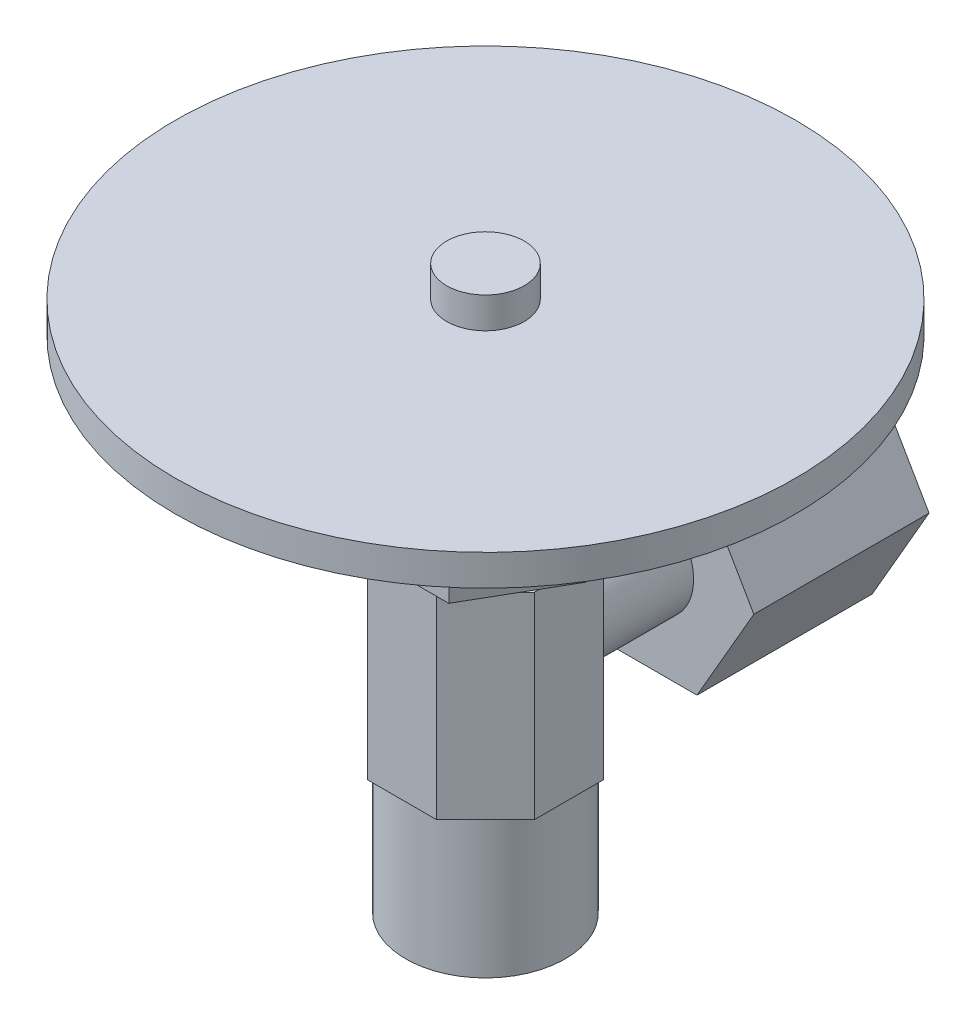
SolidWorks part; units mm, degrees
ref_plane "Front Plane" through (0, 0, 0) normal (0, 0, 1) x (1, 0, 0)
ref_plane "Top Plane" through (0, 0, 0) normal (0, 1, 0) x (1, 0, 0)
ref_plane "Right Plane" through (0, 0, 0) normal (1, 0, 0) x (0, 0, -1)
sketch "Sketch1" plane through (0, 0, 0) normal (0, 1, 0) x (1, 0, 0)
  line L0 (-2.2264, -5.375) -> (2.2264, -5.375)
  line L1 (5.375, -2.2264) -> (5.375, 2.2264)
  line L2 (5.375, 2.2264) -> (2.2264, 5.375)
  line L3 (2.2264, 5.375) -> (-2.2264, 5.375)
  line L4 (-2.2264, 5.375) -> (-5.375, 2.2264)
  line L5 (-5.375, 2.2264) -> (-5.375, -2.2264)
  line L6 (-5.375, -2.2264) -> (-2.2264, -5.375)
  line L7 (2.2264, -5.375) -> (5.375, -2.2264)
  circle A0 centre (0, 0) radius 5.375 construction
  dimension "D1" = 10.75
extrude "Boss-Extrude1" add sketch "Sketch1" along normal blind 12.7
sketch "Sketch2" plane through (0, 0, -5.375) normal (0, 0, -1) x (-1, 0, 0)
  line L0 (-2.2264, 12.7) -> (2.2264, 0) construction
  line L1 (2.2264, 0) -> (5.375, 0) construction
  line L2 (2.2264, 12.7) -> (2.2264, 0) construction
  circle A0 centre (0, 6.35) radius 3.445
extrude "Boss-Extrude2" add sketch "Sketch2" along normal blind 4.6 and the other way blind 2
sketch "Sketch3" plane through (0, 0, -9.975) normal (0, 0, -1) x (-1, 0, 0)
  line L1 (7.3323, 6.35) -> (3.6662, 12.7)
  line L2 (3.6662, 12.7) -> (-3.6662, 12.7)
  line L3 (-3.6662, 12.7) -> (-7.3323, 6.35)
  line L4 (-7.3323, 6.35) -> (-3.6662, 0)
  line L5 (-3.6662, 0) -> (3.6662, 0)
  line L6 (3.6662, 0) -> (7.3323, 6.35)
  circle A0 centre (0, 6.35) radius 6.35 construction
  dimension "D1" = 12.7
extrude "Boss-Extrude3" add sketch "Sketch3" along normal blind 11.3
sketch "Sketch4" plane through (0, 0, 0) normal (0, -1, 0) x (1, 0, 0)
  circle A0 centre (0, 0) radius 5.15
  dimension "D1" = 10.3
extrude "Boss-Extrude4" add sketch "Sketch4" along normal blind 9
sketch "Sketch5" plane through (0, 12.7, 0) normal (0, 1, 0) x (1, 0, 0)
  line L1 (6.4663, 0) -> (3.2332, 5.6)
  line L2 (3.2332, 5.6) -> (-3.2332, 5.6)
  line L3 (-3.2332, 5.6) -> (-6.4663, 0)
  line L4 (-6.4663, 0) -> (-3.2332, -5.6)
  line L5 (-3.2332, -5.6) -> (3.2332, -5.6)
  line L6 (3.2332, -5.6) -> (6.4663, 0)
  circle A0 centre (0, 0) radius 5.6 construction
  dimension "D1" = 11.2
extrude "Boss-Extrude5" add sketch "Sketch5" along normal blind 8.57
sketch "Sketch6" plane through (0, 21.27, 0) normal (0, 1, 0) x (1, 0, 0)
  circle A0 centre (0, 0) radius 2.5
  dimension "D1" = 5
extrude "Boss-Extrude6" add sketch "Sketch6" along normal blind 6
sketch "Sketch7" plane through (0, 27.27, 0) normal (0, 1, 0) x (1, 0, 0)
  circle A0 centre (0, 0) radius 20
  dimension "D1" = 40
extrude "Boss-Extrude7" add sketch "Sketch7" against normal blind 2 from offset 2 offset against normal yes
